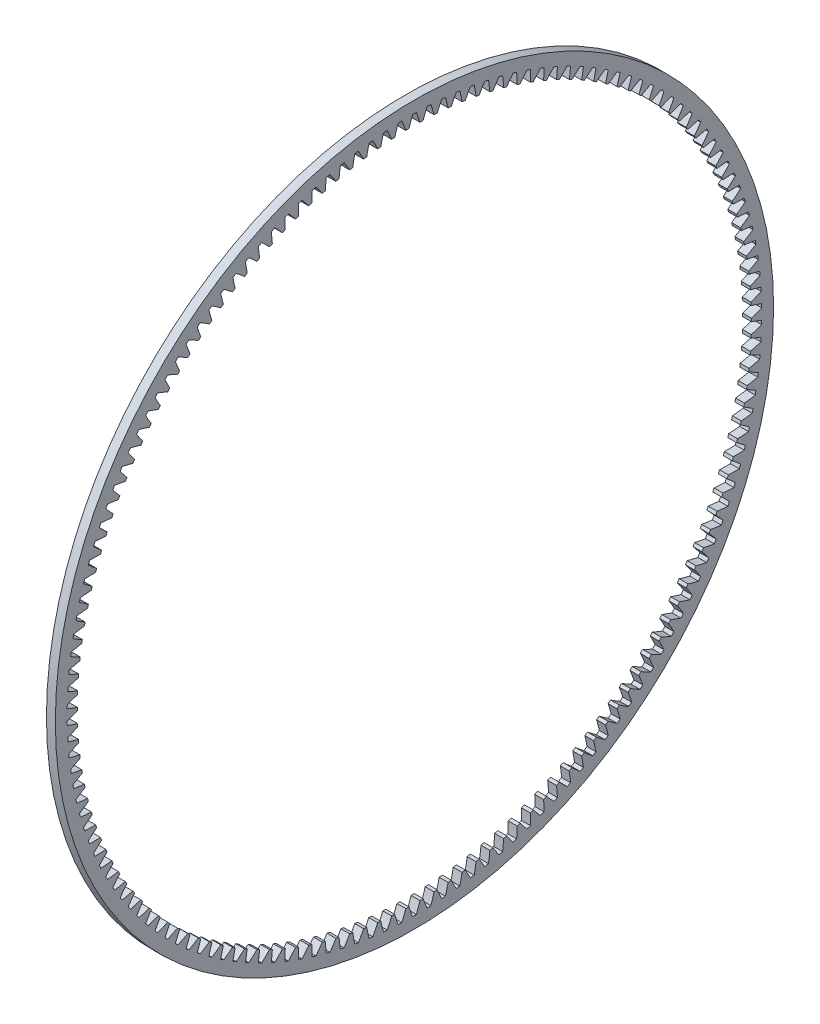
SolidWorks part; units mm, degrees
ref_plane "Plane1" through (0, 0, 0) normal (0, 0, 1) x (1, 0, 0)
ref_plane "Plane2" through (0, 0, 0) normal (0, 1, 0) x (1, 0, 0)
ref_plane "Plane3" through (0, 0, 0) normal (1, 0, 0) x (0, 0, -1)
sketch "HoldingSke" plane through (0, 0, 0) normal (0, 1, 0) x (1, 0, 0)
  line L0 (0, 0) -> (-0.1332, -0.0769)
  line L1 (-15, 0) -> (100, 0) construction
  line L2 (0, 0) -> (-2.1039, 2.3779)
  line L3 (0, 0) -> (-11.863, 4.5341)
  line L4 (0, 0) -> (-7.479, 4.318)
  line L5 (0, 0) -> (-23.7986, -8.8762)
  line L6 (0, 0) -> (-10.5278, -7.1032)
  line L7 (-2.1039, 2.3779) -> (3.3635, 27.1825)
  line L8 (-76.2, 8.8779) -> (-54.61, 8.8779)
  line L9 (-71.009, 38.7566) -> (-53.1078, 45.2721)
  line L10 (-76.2, 71.12) -> (104.1128, 71.12)
  line L11 (0, 0) -> (-12.7, 0)
  line L12 (-76.2, 101.6) -> (-75.981, 101.6)
  line L13 (24.9733, 27.94) -> (52.9518, 28.4284)
  line L14 (24.9733, 27.94) -> (24.9743, 27.94)
  line L15 (24.9733, 27.94) -> (100.4006, 29.5858)
  circle A0 centre (0, 0) radius 512.5
  circle A1 centre (0, 0) radius 12.7
  circle A2 centre (0, 0) radius 12.7
  dimension "Num_teeth" = 150
  dimension "Pitch_radius" = 180.3128
  dimension "Width" = 12.7
  dimension "Thickness" = 12.7
  dimension "Diameter" = 1025
sketch "BasProSke" plane through (0, 0, 0) normal (0, 1, 0) x (1, 0, 0)
  line L0 (-10, 0) -> (60, 0) construction
  line L1 (0, 481) -> (0, 512.5)
  line L2 (0, 481) -> (12.7, 481)
  line L3 (12.7, 481) -> (12.7, 512.5)
  line L4 (12.7, 512.5) -> (0, 512.5)
  dimension "Thickness" = 12.7
  dimension "Diameter" = 1025
revolve "Base-Revolve" add sketch "BasProSke" angle 360 about L0
sketch "TooCutSke" plane through (0, 0, 0) normal (1, 0, 0) x (0, 0, -1)
  line L3 (5.6525, 487.4672) -> (5.6525, 53.6633) construction
  line L4 (0, 0) -> (0, 59.563) construction
  line L5 (0, 0) -> (-1.4309, 68.3125) construction
  line L6 (-224.6672, 407.6745) -> (29.2002, 412.9922) construction
  circle A0 centre (0, 0) radius 487.5 construction
  circle A1 centre (0, 0) radius 495.626 construction
  circle A2 centre (0, 0) radius 412.2901 construction
  circle A3 centre (0, 0) radius 480.9746 construction
  arc A4 (7.8203, 480.911) -> (2.6648, 495.6188) centre (-224.6672, 407.6745) ccw
  arc A5 (7.8203, 480.911) -> (-7.8203, 480.911) centre (0, 0) ccw
  arc A6 (2.6648, 495.6188) -> (-2.6648, 495.6188) centre (0, 0) ccw
  arc A7 (-2.6648, 495.6188) -> (-7.8203, 480.911) centre (224.6672, 407.6745) ccw
extrude "ToothCut" cut sketch "TooCutSke" along normal through all
fillet "Breaks" [suppressed] radius 0.65
fillet "RootFillets" [suppressed] radius 1.626
pattern_circular "TeethCuts" count 150 every 2.4 about axis through (-10, 0, 0) along (1, 0, 0) of "RootFillets", "Breaks", "ToothCut"
sketch "Sketch1" plane through (0, 0, 0) normal (-1, 0, 0) x (0, 0, 1)
  circle A0 centre (0, 0) radius 487.5
equation "' \"Module@HoldingSke\" = 6.35"
equation "' \"Num_teeth@HoldingSke\" = 24"
equation "' \"Ap@HoldingSke\" =  14.5"
equation "' \"Ap@HoldingSke\" = 14.5"
equation "' \"Width@HoldingSke\" = 12"
equation "' \"Diameter@HoldingSke\" = 8 * 25.4"
equation "' \"Show_teeth@HoldingSke\" = 100"
equation "' \"Backlash@HoldingSke\" = 0.009 * 25.4"
equation "' \"Addendum_fac@HoldingSke\" = 1.0"
equation "' \"Dedendum_fac@HoldingSke\" = 1.25"
equation "' \"Dedendum_add@HoldingSke\" = 0.00005 * 25.4"
equation "' \"Clearance_fac@HoldingSke\" = 0.25"
equation "\"Pitch@HoldingSke\" = 1 / \"Module@HoldingSke\" "
equation "\"Overcut_dia@TooCutSke\" = (\"Num_teeth@HoldingSke\" - 2 * \"Addendum_fac@HoldingSke\") / \"Pitch@HoldingSke\" - 0.002 * 25.4"
equation "\"Pitch_dia@TooCutSke\" = \"Num_teeth@HoldingSke\" / \"Pitch@HoldingSke\""
equation "\"Base_dia@TooCutSke\" = \"Num_teeth@HoldingSke\" / \"Pitch@HoldingSke\" * cos((\"Ap@HoldingSke\"  * 3.14159265 / 180)) * 0.90"
equation "\"Root_dia@TooCutSke\" = \"Num_teeth@HoldingSke\"  / \"Pitch@HoldingSke\" + 2 *  \"Dedendum_fac@HoldingSke\"/ \"Pitch@HoldingSke\" + \"Dedendum_add@HoldingSke\" * 2"
equation "\"Half_ang@TooCutSke\" = 180 / \"Num_teeth@HoldingSke\""
equation "\"Half_CT@TooCutSke\" = \"Num_teeth@HoldingSke\" / \"Pitch@HoldingSke\" * sin((3.14159265 / 2 / \"Num_teeth@HoldingSke\")) / 2 + 10 * \"Backlash@HoldingSke\" / 4"
equation "\"Flank_rad@TooCutSke\" = \"Num_teeth@HoldingSke\" / \"Pitch@HoldingSke\" / 4"
equation "\"Radius@RootFillets\"= \"Clearance_fac@HoldingSke\" / \"Pitch@HoldingSke\" + \"Dedendum_add@HoldingSke\""
equation "\"Break_rad@Breaks\" = 0.02 / \"Pitch@HoldingSke\" * 5"
equation "\"Num_teeth@TeethCuts\" = int( \"Show_teeth@HoldingSke\" ) + 1"
equation "\"Num_teeth@TeethCuts\" = ((sgn( \"Num_teeth@TeethCuts\" - \"Num_teeth@HoldingSke\" )-1)*( \"Num_teeth@TeethCuts\" - \"Num_teeth@HoldingSke\" ))/-2+ \"Num_teeth@HoldingSke\""
equation "\"Num_teeth@TeethCuts\" = ((sgn( \"Num_teeth@TeethCuts\" - 2.0)+1)*( \"Num_teeth@TeethCuts\" - 2.0))/2 +2.0"
equation "\"Angle@TeethCuts\" = 360.0 / \"Num_teeth@HoldingSke\""
equation "\"Diameter@BasProSke\" = \"Num_teeth@HoldingSke\"  / \"Pitch@HoldingSke\" + 2 *  \"Dedendum_fac@HoldingSke\"/ \"Pitch@HoldingSke\" + \"Dedendum_add@HoldingSke\" * 2 + 0.002 * 25.4"
equation "\"Diameter@BasProSke\" = ((sgn( \"Diameter@BasProSke\"  - \"Diameter@HoldingSke\" )+1)*( \"Diameter@BasProSke\"  - \"Diameter@HoldingSke\" ))/2 + \"Diameter@HoldingSke\""
equation "\"Inside_diameter@BasProSke\" =  (\"Num_teeth@HoldingSke\" - 2 * \"Addendum_fac@HoldingSke\") / \"Pitch@HoldingSke\" "
equation "\"Thickness@BasProSke\"  = \"Width@HoldingSke\""
